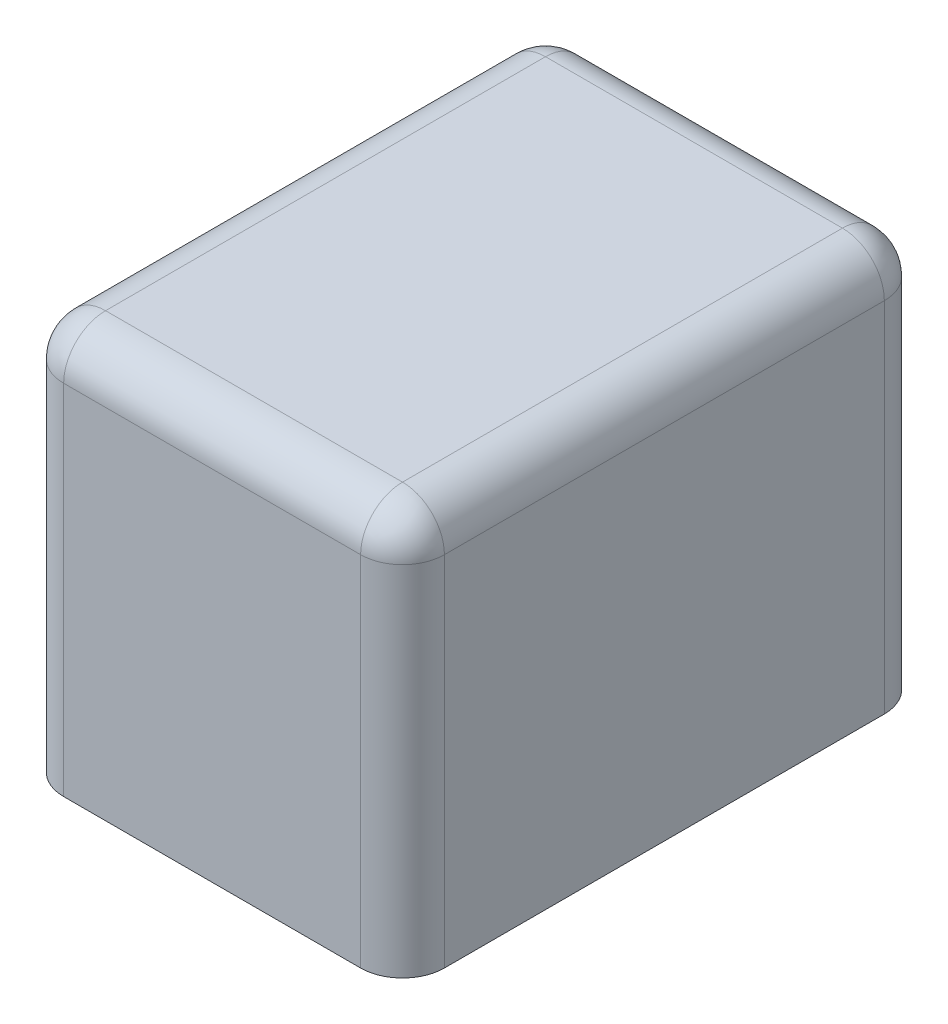
SolidWorks part; units mm, degrees
ref_plane "Front Plane" through (0, 0, 0) normal (0, 0, 1) x (1, 0, 0)
ref_plane "Top Plane" through (0, 0, 0) normal (0, 1, 0) x (1, 0, 0)
ref_plane "Right Plane" through (0, 0, 0) normal (1, 0, 0) x (0, 0, -1)
sketch "Sketch1" plane through (0, 0, 0) normal (0, 1, 0) x (1, 0, 0)
  line L1 (-18.175, 25) -> (18.175, 25)
  line L2 (-18.175, 25) -> (-18.175, -25)
  line L3 (-18.175, -25) -> (18.175, -25)
  line L4 (18.175, 25) -> (18.175, -25)
  line L5 (-18.175, 25) -> (18.175, -25) construction
  line L6 (-18.175, -25) -> (18.175, 25) construction
  line L7 (-15, 21.825) -> (15, 21.825)
  line L8 (-15, 21.825) -> (-15, -21.825)
  line L9 (-15, -21.825) -> (15, -21.825)
  line L10 (15, 21.825) -> (15, -21.825)
  line L11 (-15, 21.825) -> (15, -21.825) construction
  line L12 (-15, -21.825) -> (15, 21.825) construction
  point P0 (0, 0)
  point P6 (0, 0)
  dimension "D1" = 3.175
  dimension "D2" = 3.175
  dimension "D3" = 30
  dimension "D4" = 50
extrude "Boss-Extrude1" add sketch "Sketch1" along normal blind 35
sketch "Sketch2" plane through (0, 35, 0) normal (0, 1, 0) x (1, 0, 0)
  line L1 (-18.175, -25) -> (18.175, -25)
  line L2 (-18.175, -25) -> (-18.175, 25)
  line L3 (-18.175, 25) -> (18.175, 25)
  line L4 (18.175, -25) -> (18.175, 25)
extrude "Boss-Extrude2" add sketch "Sketch2" along normal blind 3.175
sketch "Sketch4" plane through (0, 0, 0) normal (0, -1, 0) x (1, 0, 0)
  line L0 (0, 25) -> (0, -25) construction
  line L1 (-18.175, 25) -> (18.175, 25) construction
  line L2 (18.175, -25) -> (-18.175, -25) construction
  line L3 (-18.175, 0) -> (18.175, 0) construction
  line L4 (-18.175, -25) -> (-18.175, 25) construction
  line L5 (18.175, 25) -> (18.175, -25) construction
  line L17 (-3.6, -20) -> (-3.6, -21.825)
  line L18 (15, -21.825) -> (-15, -21.825) construction
  line L19 (3.6, -20) -> (3.6, -21.825)
  line L20 (-3.6, 21.825) -> (3.6, 21.825)
  line L21 (3.6, 20) -> (3.6, 21.825)
  line L22 (-3.6, -21.825) -> (3.6, -21.825)
  line L23 (-3.6, 20) -> (-3.6, 21.825)
  arc A4 (3.6, -20) -> (-3.6, -20) centre (0, -20) ccw
  arc A5 (3.6, 20) -> (-3.6, 20) centre (0, 20) cw
  dimension "D1" = 7.2
  dimension "D2" = 5
extrude "Boss-Extrude3" add sketch "Sketch4" against normal blind 5
fillet "Fillet1" radius 4 8 edges at (-18.175, 38.175, 0) (-18.175, 19.0875, -25) (0, 38.175, -25) (18.175, 19.0875, -25) (18.175, 38.175, 0) (0, 38.175, 25) (18.175, 19.0875, 25) (-18.175, 19.0875, 25)
sketch "Sketch6" plane through (-18.175, 0, 0) normal (-1, 0, 0) x (0, 0, 1)
  line L0 (0, 34.175) -> (0, 0) construction
  line L5 (21, 34.175) -> (-21, 34.175) construction
  line L8 (-21, 0) -> (21, 0) construction
  line L9 (-10, 18.175) -> (0, 18.175) construction
  line L10 (-5, 23.175) -> (5, 23.175)
  line L11 (-5, 23.175) -> (-5, 18.175)
  line L12 (-5, 18.175) -> (5, 18.175)
  line L13 (5, 23.175) -> (5, 18.175)
  line L14 (-5, 23.175) -> (5, 18.175) construction
  line L15 (-5, 18.175) -> (5, 23.175) construction
  point P6 (0, 20.675)
  dimension "D1" = 10
  dimension "D2" = 5
  dimension "D3" = 0
extrude "Cut-Extrude3" cut sketch "Sketch6" against normal blind 3.175
sketch "Sketch8" plane through (0, 0, 0) normal (0, -1, 0) x (1, 0, 0)
  line L0 (-18.175, 0) -> (18.175, 0) construction
  line L1 (-18.175, -21) -> (-18.175, 21) construction
  line L2 (18.175, 21) -> (18.175, -21) construction
  circle A0 centre (0, -20) radius 3.05
  circle A1 centre (0, 20) radius 3.05
  dimension "D1" = 6.1
extrude "Cut-Extrude5" cut sketch "Sketch8" against normal blind 2.7
sketch "Sketch9" plane through (18.175, 0, 0) normal (1, 0, 0) x (0, 0, -1)
  line L0 (0, 34.175) -> (0, 0) construction
  line L2 (-21, 0) -> (21, 0) construction
  line L3 (16.5, 11.9938) -> (16.5, 7.9937)
  line L4 (-12.25, 11.9938) -> (-6.25, 11.9938)
  line L5 (-12.25, 11.9938) -> (-12.25, 7.9938)
  line L6 (-12.25, 7.9938) -> (-6.25, 7.9938)
  line L7 (-6.25, 11.9938) -> (-6.25, 7.9938)
  line L8 (22.5, 7.9937) -> (16.5, 7.9937)
  line L9 (22.5, 11.9938) -> (22.5, 7.9937)
  line L10 (22.5, 11.9938) -> (16.5, 11.9938)
  line L11 (21, 34.175) -> (-21, 34.175) construction
  dimension "D1" = 6
  dimension "D2" = 4
  dimension "D4" = 7.9938
  dimension "D3" = 22.75
  dimension "D5" = 6.25
  dimension "D7" = 0
  dimension "D8" = 4
  dimension "D6" = 6
extrude "Boss-Extrude4" add sketch "Sketch9" against normal blind 12.5 from surface starting at face at (15, 17.5, 0)
sketch "Sketch10" plane through (0, 7.9938, 0) normal (0, -1, 0) x (1, 0, 0)
  line L0 (-16.5229, 0) -> (15.3543, 0) construction
  line L1 (15, 21.825) -> (15, -21.825) construction
  circle A0 centre (8.75, 8.575) radius 1
  circle A1 centre (8.75, -18.825) radius 1
  dimension "D3" = 2
  dimension "D1" = 27.4
  dimension "D2" = 6.25
  dimension "D4" = 8.575
extrude "Cut-Extrude6" cut sketch "Sketch10" against normal blind 15.675
equation "\"D8@Sketch9\"=\"D2@Sketch9\""
equation "\"D6@Sketch9\"=\"D1@Sketch9\""
